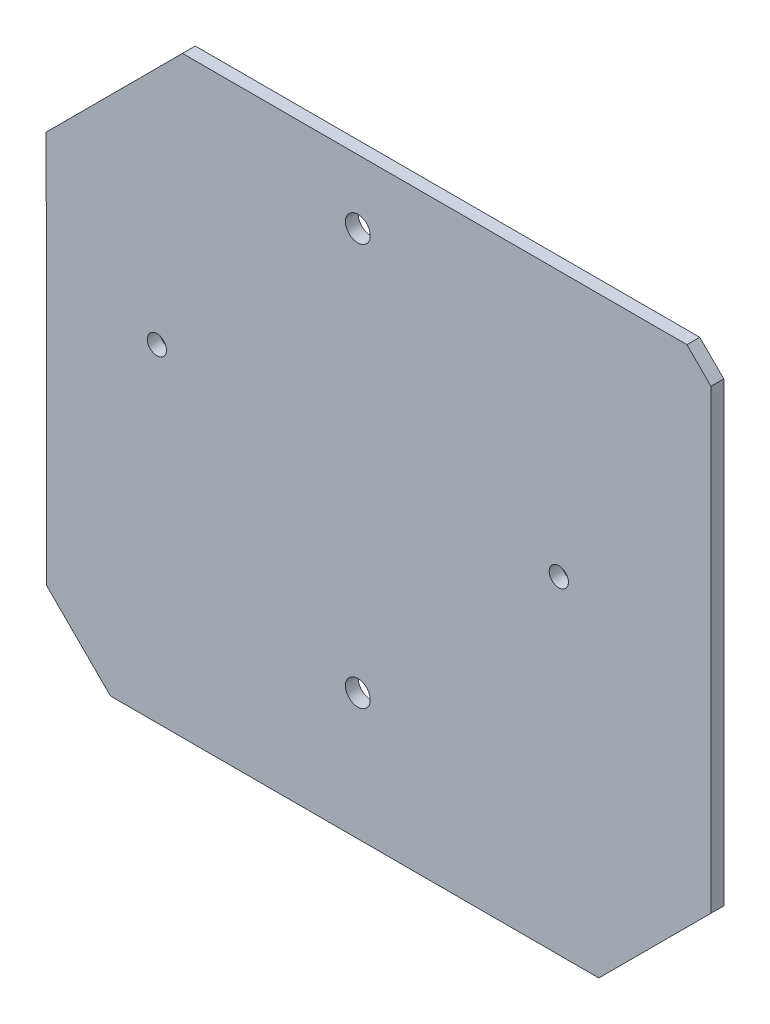
SolidWorks part; units mm, degrees
material "FR4_stuffedProtoboard"
ref_plane "Front Plane" through (0, 0, 0) normal (0, 0, 1) x (1, 0, 0)
ref_plane "Top Plane" through (0, 0, 0) normal (0, 1, 0) x (1, 0, 0)
ref_plane "Right Plane" through (0, 0, 0) normal (1, 0, 0) x (0, 0, -1)
sketch "Imported DXF" plane through (0, 0, 0) normal (0, 0, 1) x (1, 0, 0)
  line L0 (-21.6929, 33.1) -> (40.8929, 33.1)
  line L1 (41.2464, 32.9535) -> (43.9536, 30.2464)
  line L2 (44.1, 29.8929) -> (44.1, -26.6929)
  line L3 (43.9535, -27.0465) -> (30.2464, -40.7536)
  line L4 (29.8929, -40.9) -> (-30.6929, -40.9)
  line L5 (-31.0465, -40.7536) -> (-38.7536, -33.0464)
  line L6 (-38.9001, -32.6946) -> (-38.9148, 15.8797)
  line L7 (-38.7685, 16.2316) -> (-22.0464, 32.9536)
  line L8 (34.175, 6.26) -> (32.925, 6.26)
  line L9 (32.925, 6.26) -> (32.925, 8.26)
  line L10 (32.925, 8.26) -> (34.175, 8.26)
  line L11 (34.175, 8.26) -> (34.175, 6.26)
  line L12 (5.75, 8.485) -> (5.75, 9.735)
  line L13 (5.75, 9.735) -> (7.75, 9.735)
  line L14 (7.75, 9.735) -> (7.75, 8.485)
  line L15 (7.75, 8.485) -> (5.75, 8.485)
  line L16 (-4.91, -8.495) -> (-4.91, -9.745)
  line L17 (-4.91, -9.745) -> (-6.91, -9.745)
  line L18 (-6.91, -9.745) -> (-6.91, -8.495)
  line L19 (-6.91, -8.495) -> (-4.91, -8.495)
  line L20 (39.91, -3.075) -> (32.29, -3.075)
  line L21 (32.29, 3.275) -> (39.91, 3.275)
  line L22 (32.671, -3.075) -> (32.29, -3.075)
  line L23 (32.29, -3.075) -> (32.29, 3.275)
  line L24 (32.29, 3.275) -> (32.671, 3.275)
  line L25 (39.529, -3.075) -> (39.91, -3.075)
  line L26 (39.91, -3.075) -> (39.91, 3.275)
  line L27 (39.91, 3.275) -> (39.529, 3.275)
  line L28 (-3.81, 15.275) -> (3.81, 15.275)
  line L29 (3.81, 8.925) -> (-3.81, 8.925)
  line L30 (3.429, 15.275) -> (3.81, 15.275)
  line L31 (3.81, 15.275) -> (3.81, 8.925)
  line L32 (3.81, 8.925) -> (3.429, 8.925)
  line L33 (-3.429, 15.275) -> (-3.81, 15.275)
  line L34 (-3.81, 15.275) -> (-3.81, 8.925)
  line L35 (-3.81, 8.925) -> (-3.429, 8.925)
  line L36 (3.81, -15.275) -> (-3.81, -15.275)
  line L37 (-3.81, -8.925) -> (3.81, -8.925)
  line L38 (-3.429, -15.275) -> (-3.81, -15.275)
  line L39 (-3.81, -15.275) -> (-3.81, -8.925)
  line L40 (-3.81, -8.925) -> (-3.429, -8.925)
  line L41 (3.429, -15.275) -> (3.81, -15.275)
  line L42 (3.81, -15.275) -> (3.81, -8.925)
  line L43 (3.81, -8.925) -> (3.429, -8.925)
  line L44 (0, 37.7984) -> (0, -46.2816) construction
  line L45 (-65.7891, 0) -> (80.4964, 0) construction
  arc A0 (41.2464, 32.9535) -> (40.8929, 33.1) centre (40.8929, 32.6) ccw
  arc A1 (44.1, 29.8929) -> (43.9535, 30.2464) centre (43.6, 29.8929) ccw
  arc A2 (43.9535, -27.0465) -> (44.1, -26.6929) centre (43.6, -26.6929) ccw
  arc A3 (29.8929, -40.9) -> (30.2464, -40.7536) centre (29.8929, -40.4) ccw
  arc A4 (-31.0465, -40.7536) -> (-30.6929, -40.9) centre (-30.6929, -40.4) ccw
  arc A5 (-38.9001, -32.6946) -> (-38.7537, -33.0464) centre (-38.4001, -32.6928) ccw
  arc A6 (-38.7685, 16.2316) -> (-38.9149, 15.8796) centre (-38.4155, 15.8783) ccw
  arc A7 (-21.6929, 33.1) -> (-22.0465, 32.9535) centre (-21.6929, 32.6) ccw
  circle A8 centre (-25.1, 0) radius 1.2
  circle A9 centre (25.1, 0) radius 1.2
  circle A10 centre (0, 25.1) radius 1.55
  circle A11 centre (0, -25.1) radius 1.55
  circle A12 centre (40.481, 2.989) radius 0.254
  circle A13 centre (-4.381, 9.211) radius 0.254
  circle A14 centre (4.381, -9.211) radius 0.254
  point P20 (0, 0)
  point P40 (33.55, 7.26)
  point P45 (6.75, 9.11)
  point P50 (-5.91, -9.12)
  point P55 (38.1, 26.1)
  point P56 (23.4, 23.4)
  point P57 (-23.4, 23.4)
  point P58 (-23.4, -23.4)
  point P59 (23.4, -23.4)
  point P60 (36.1, 0.1)
  point P71 (0, 12.1)
  point P82 (0, -12.1)
  dimension "D1" = 3.1
sketch "Outline" plane through (0, 0, 0) normal (0, 0, 1) x (1, 0, 0)
  line L0 (-21.9, 33.1) -> (41.1, 33.1)
  line L2 (44.1, -26.9) -> (30.1, -40.9)
  line L3 (30.1, -40.9) -> (-30.9, -40.9)
  line L4 (-30.9, -40.9) -> (-38.9, -32.9)
  line L5 (-38.9, -32.9) -> (-38.9149, 16.0852)
  line L6 (-38.9149, 16.0852) -> (-21.9, 33.1)
  line L7 (-38.7685, 16.2316) -> (-22.0464, 32.9536) construction
  line L8 (-21.6929, 33.1) -> (40.8929, 33.1) construction
  line L13 (-38.9001, -32.6946) -> (-38.9148, 15.8797) construction
  line L14 (-31.0465, -40.7536) -> (-38.7536, -33.0464) construction
  line L15 (29.8929, -40.9) -> (-30.6929, -40.9) construction
  line L16 (43.9535, -27.0465) -> (30.2464, -40.7536) construction
  line L18 (41.1, 33.1) -> (44.1, 30.1)
  line L19 (44.1, 30.1) -> (44.1, -26.9)
  line L20 (44.1, 29.8929) -> (44.1, -26.6929) construction
  line L21 (41.2464, 32.9535) -> (43.9536, 30.2464) construction
extrude "Boss-Extrude1" add sketch "Outline" along normal blind 1.6
sketch "Connector locations" plane through (0, 0, 1.6) normal (0, 0, 1) x (1, 0, 0)
  line L1 (24.5314, 22.2686) -> (22.2686, 24.5314)
  line L2 (38.1, 27.7) -> (38.1, 24.5)
  line L3 (22.2686, -24.5314) -> (24.5314, -22.2686)
  line L4 (0, 0) -> (23.4, 23.4) construction
  line L5 (-24.5314, -22.2686) -> (-22.2686, -24.5314)
  line L6 (-22.2686, 24.5314) -> (-24.5314, 22.2686)
  line L9 (-21.6929, 33.1) -> (40.8929, 33.1) construction
  line L10 (-65.7891, 0) -> (80.4964, 0) construction
  point P13 (38.1, 26.1)
  dimension "D1" = 45
  dimension "D3" = 45
  dimension "D4" = 33.0926
  dimension "D6" = 3.2
sketch "Sketch3" plane through (0, 0, 1.6) normal (0, 0, 1) x (1, 0, 0)
  circle A0 centre (0, 25.1) radius 1.55
  circle A1 centre (25.1, 0) radius 1.2
  circle A2 centre (0, -25.1) radius 1.55
  circle A3 centre (-25.1, 0) radius 1.2
  circle A4 centre (25.1, 0) radius 1.2 construction
  circle A5 centre (0, 25.1) radius 1.55 construction
  circle A6 centre (-25.1, 0) radius 1.2 construction
  circle A7 centre (0, -25.1) radius 1.55 construction
extrude "Cut-Extrude3" cut sketch "Sketch3" against normal up to next
